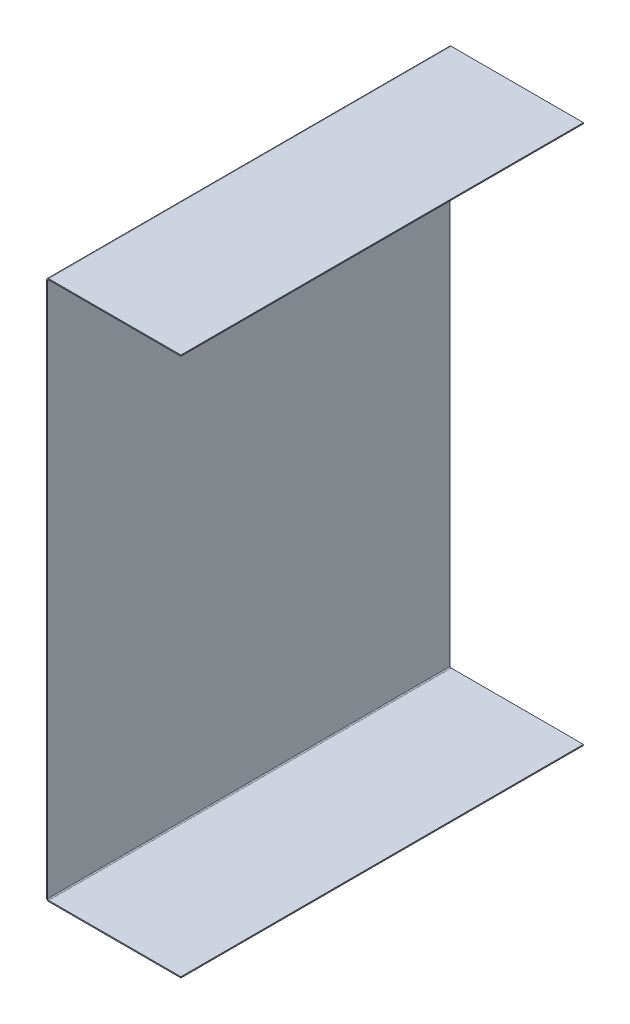
SolidWorks part; units mm, degrees
note: The reader was unsure of these and kept them because the rebuilt part matched: thickness of "Base-Flange1", "Edge-Flange1", "Sheet-Metal1", "Sheet-Metal2"; flange length of "Edge-Flange1".
material "1.0037 (S235JR)"
ref_plane "Front Plane" through (0, 0, 0) normal (1, 0, 0) x (0, 1, 0)
ref_plane "Top Plane" through (0, 0, 0) normal (0, 0, 1) x (0, 1, 0)
ref_plane "Right Plane" through (0, 0, 0) normal (0, 1, 0) x (-1, 0, 0)
sketch "Sketch1" plane through (0, 0, 0) normal (1, 0, 0) x (0, 1, 0)
  line L1 (496, -373) -> (-496, -373)
  line L2 (496, -373) -> (496, 373)
  line L3 (496, 373) -> (-496, 373)
  line L4 (-496, -373) -> (-496, 373)
  line L5 (496, -373) -> (-496, 373) construction
  line L6 (496, 373) -> (-496, -373) construction
  point P0 (0, 0)
  dimension "D1" = 746
  dimension "D2" = 992
base flange "Base-Flange1" sketch "Sketch1" thickness 2 reverse thickness direction no parameters "D1"=2
edge flange "Edge-Flange1" sketch "Sketch10" flange profiles "Sketch10", "Sketch11" flange angle 90 flange length 249 flange position bend outside bend radius 2 thickness 2 relief rectangular parameters "D1"=1, "D6"=10, "D8"=0.1
sketch "Sketch10" plane through (0, 496, 0) normal (0, -1, 0) x (0, 0, -1)
  line L2 (-373, 0) -> (-373, 247)
  line L3 (-373, 247) -> (373, 247)
  line L4 (373, 247) -> (373, 0)
  line L5 (373, 0) -> (-373, 0) construction
  line L6 (373, 0) -> (-373, 0)
  dimension "D1" = 90
sketch "Sketch11" plane through (0, -496, 0) normal (0, 1, 0) x (0, 0, 1)
  line L0 (373, 0) -> (-373, 0) construction
  line L1 (373, 0) -> (-373, 0)
  line L2 (373, 0) -> (373, 247)
  line L3 (373, 247) -> (-373, 247)
  line L4 (-373, 247) -> (-373, 0)
  dimension "D1" = 90
bend "EdgeBend1" bend radius 2 bend angle 90 parameters "D5"=1
bend "EdgeBend2" bend radius 2 bend angle 90 parameters "D5"=2
sketch "Bend-Lines1" [suppressed] plane through (0, 0, 0) normal (0, 1, 0) x (-1, 0, 0)
sketch "Bounding-Box1" [suppressed] plane through (0, 0, 0) normal (0, 1, 0) x (-1, 0, 0)
sheet metal parameters "Sheet-Metal1" thickness 2 parameters "D1"=2
flat pattern "Flat-Pattern1" [suppressed]
sketch "Bend-Lines2" plane through (0, 0, 0) normal (0, 1, 0) x (-1, 0, 0)
sketch3d "Bounding-Box2" [suppressed]
  line L0 (-498, -375, 0) -> (498, -375, 0) construction
  line L1 (-498, 375, 0) -> (498, 375, 0) construction
  line L2 (-498, -375, 0) -> (-498, 375, 0) construction
  line L3 (498, -375, 0) -> (498, 375, 0) construction
sheet metal parameters "Sheet-Metal2" thickness 2 parameters "D1"=2, "D7"=1
flat pattern "Flat-Pattern1"
sketch "Bend-Lines2" plane through (0, 0, 0) normal (1, 0, 0) x (0, 1, 0)
  line L0 (-498.0735, 373) -> (-498.0735, -373) construction
  line L1 (498.0735, -373) -> (498.0735, 373) construction
  line L2 (-498.0735, 373) -> (-498.0735, -373) construction
  line L3 (498.0735, -373) -> (498.0735, 373) construction
sketch3d "Bounding-Box2" [suppressed]
  line L0 (745.1469, -373, 0) -> (-745.1469, -373, 0) construction
  line L1 (745.1469, 373, 0) -> (-745.1469, 373, 0) construction
  line L2 (745.1469, -373, 0) -> (745.1469, 373, 0) construction
  line L3 (-745.1469, -373, 0) -> (-745.1469, 373, 0) construction
bend of the flat pattern "Flatten-<EdgeBend1>1"
bend of the flat pattern "Flatten-<EdgeBend2>1"
